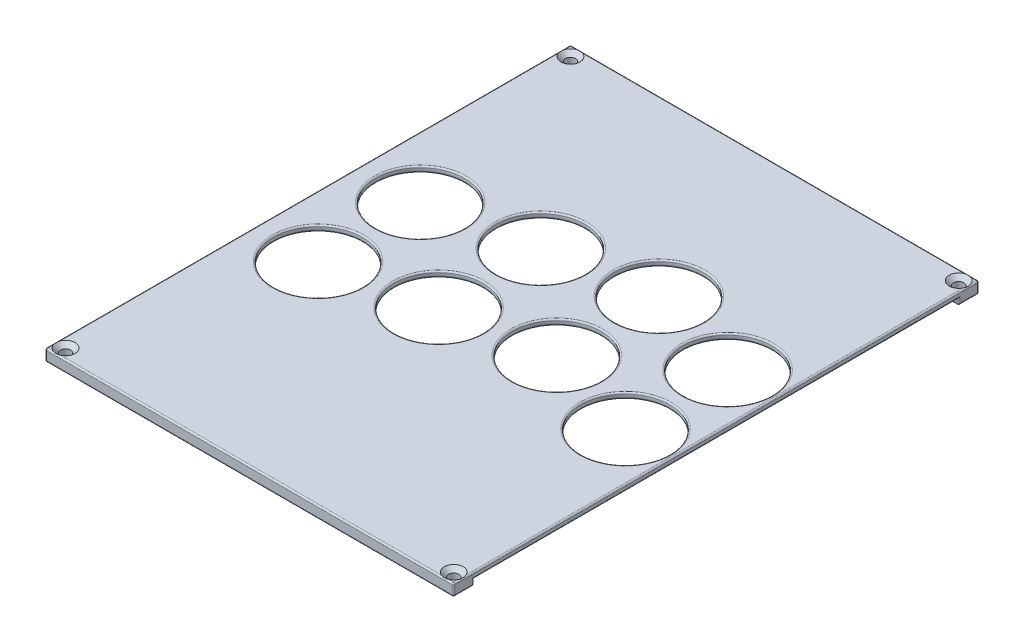
SolidWorks part; units mm, degrees
ref_plane "Front Plane" through (0, 0, 0) normal (0, 0, 1) x (1, 0, 0)
ref_plane "Top Plane" through (0, 0, 0) normal (0, 1, 0) x (1, 0, 0)
ref_plane "Right Plane" through (0, 0, 0) normal (1, 0, 0) x (0, 0, -1)
sketch "Sketch1" plane through (0, 0, 0) normal (0, 1, 0) x (1, 0, 0)
  line L0 (-119, -72.5) -> (-84.7071, -65.5) construction
  line L1 (0, 0) -> (-140, 0)
  line L2 (0, 0) -> (0, -180)
  line L3 (0, -180) -> (-140, -180)
  line L4 (-140, 0) -> (-140, -180)
  line L5 (-84.7071, -65.5) -> (-50.2253, -59.5) construction
  line L6 (-50.2253, -59.5) -> (-16.6842, -69.5) construction
  line L7 (-16.6842, -69.5) -> (-16.6842, -104.5) construction
  line L8 (-16.6842, -104.5) -> (-50.2253, -94.5) construction
  line L9 (-50.2253, -94.5) -> (-84.7071, -100.5) construction
  line L10 (-84.7071, -100.5) -> (-119, -107.5) construction
  line L11 (-119, -107.5) -> (-119, -72.5) construction
  line L12 (-84.7071, -100.5) -> (-84.7071, -65.5) construction
  line L13 (-50.2253, -94.5) -> (-50.2253, -59.5) construction
  line L14 (-16.6842, -69.5) -> (-16.6842, -59.5) construction
  line L15 (-16.6842, -59.5) -> (-50.2253, -59.5) construction
  line L16 (-50.2253, -59.5) -> (-84.7071, -59.5) construction
  line L17 (-84.7071, -65.5) -> (-84.7071, -59.5) construction
  line L18 (-84.7071, -65.5) -> (-119, -65.5) construction
  line L19 (-119, -65.5) -> (-119, -72.5) construction
  line L20 (-119, -72.5) -> (-140, -72.5) construction
  line L21 (-119, -72.5) -> (-119, 0) construction
  line L22 (-16.6842, -69.5) -> (0, -69.5) construction
  line L23 (-70, -145) -> (-140, -145) construction
  line L24 (-140, -173) -> (-133, -173) construction
  line L25 (-133, -173) -> (-133, -180) construction
  line L26 (-7, -180) -> (-7, -173) construction
  line L27 (-7, -173) -> (0, -173) construction
  line L28 (0, -7) -> (-7, -7) construction
  line L29 (-7, -7) -> (-7, 0) construction
  line L30 (-133, 0) -> (-133, -7) construction
  line L31 (-133, -7) -> (-140, -7) construction
  line L32 (-133, -7) -> (-140, 0) construction
  line L33 (-7, -7) -> (0, 0) construction
  line L34 (-7, -173) -> (0, -180) construction
  line L35 (-140, -180) -> (-133, -173) construction
  line L36 (-119, -107.5) -> (-119, -180) construction
  line L37 (-42.5, -162) -> (-97.5, -162) construction
  line L38 (-42.5, -162) -> (-42.5, -128) construction
  line L39 (-42.5, -128) -> (-97.5, -128) construction
  line L40 (-97.5, -162) -> (-97.5, -128) construction
  line L41 (-42.5, -162) -> (-97.5, -128) construction
  line L42 (-42.5, -128) -> (-97.5, -162) construction
  line L43 (-70, -145) -> (0, -145) construction
  line L44 (-70, -145) -> (-70, -180) construction
  line L45 (-133, -2) -> (-7, -2)
  line L46 (-95.1329, -128) -> (-96.3164, -125.95)
  line L47 (-96.3164, -125.95) -> (-98.6836, -125.95)
  line L48 (-98.6836, -125.95) -> (-99.8671, -128)
  line L49 (-99.8671, -128) -> (-98.6836, -130.05)
  line L50 (-98.6836, -130.05) -> (-96.3164, -130.05)
  line L51 (-96.3164, -130.05) -> (-95.1329, -128)
  line L52 (-40.1329, -128) -> (-41.3164, -125.95)
  line L53 (-41.3164, -125.95) -> (-43.6836, -125.95)
  line L54 (-43.6836, -125.95) -> (-44.8671, -128)
  line L55 (-44.8671, -128) -> (-43.6836, -130.05)
  line L56 (-43.6836, -130.05) -> (-41.3164, -130.05)
  line L57 (-41.3164, -130.05) -> (-40.1329, -128)
  line L58 (-41.3164, -164.05) -> (-40.1329, -162)
  line L59 (-40.1329, -162) -> (-41.3164, -159.95)
  line L60 (-41.3164, -159.95) -> (-43.6836, -159.95)
  line L61 (-43.6836, -159.95) -> (-44.8671, -162)
  line L62 (-44.8671, -162) -> (-43.6836, -164.05)
  line L63 (-43.6836, -164.05) -> (-41.3164, -164.05)
  line L64 (-95.1329, -162) -> (-96.3164, -159.95)
  line L65 (-96.3164, -159.95) -> (-98.6836, -159.95)
  line L66 (-98.6836, -159.95) -> (-99.8671, -162)
  line L67 (-99.8671, -162) -> (-98.6836, -164.05)
  line L68 (-98.6836, -164.05) -> (-96.3164, -164.05)
  line L69 (-96.3164, -164.05) -> (-95.1329, -162)
  line L70 (-101, -166) -> (-39, -166)
  line L71 (-101, -166) -> (-101, -124)
  line L72 (-101, -124) -> (-39, -124)
  line L73 (-39, -166) -> (-39, -124)
  line L74 (-101, -166) -> (-39, -124) construction
  line L75 (-101, -124) -> (-39, -166) construction
  line L76 (-138, -7) -> (-138, -173)
  line L77 (-133, -178) -> (-7, -178)
  line L78 (-133, -2) -> (-133, -7)
  line L79 (-133, -7) -> (-138, -7)
  line L80 (-7, -2) -> (-7, -7)
  line L81 (-7, -7) -> (0, -7)
  line L82 (0, -173) -> (-7, -173)
  line L83 (-7, -173) -> (-7, -178)
  line L84 (-133, -178) -> (-133, -173)
  line L85 (-133, -173) -> (-138, -173)
  circle A16 centre (-119, -72.5) radius 15 construction
  circle A17 centre (-84.7071, -65.5) radius 15 construction
  circle A18 centre (-50.2253, -59.5) radius 15 construction
  circle A19 centre (-16.6842, -69.5) radius 15 construction
  circle A20 centre (-119, -107.5) radius 15 construction
  circle A21 centre (-84.7071, -100.5) radius 15 construction
  circle A22 centre (-50.2253, -94.5) radius 15 construction
  circle A23 centre (-16.6842, -104.5) radius 15 construction
  circle A24 centre (-119, -72.5) radius 15.2
  circle A25 centre (-84.7071, -65.5) radius 15.2
  circle A26 centre (-50.2253, -59.5) radius 15.2
  circle A27 centre (-16.6842, -69.5) radius 15.2
  circle A28 centre (-16.6842, -104.5) radius 15.2
  circle A29 centre (-50.2253, -94.5) radius 15.2
  circle A30 centre (-84.7071, -100.5) radius 15.2
  circle A31 centre (-119, -107.5) radius 15.2
  circle A32 centre (-136.5, -3.5) radius 1.75
  circle A33 centre (-3.5, -3.5) radius 1.75
  circle A34 centre (-3.5, -176.5) radius 1.75
  circle A35 centre (-136.5, -176.5) radius 1.75
  circle A36 centre (-97.5, -128) radius 2.05 construction
  circle A37 centre (-42.5, -128) radius 2.05 construction
  circle A38 centre (-42.5, -162) radius 2.05 construction
  circle A39 centre (-97.5, -162) radius 2.05 construction
  point P23 (-70, -145)
  dimension "D1" = 30
  dimension "D7" = 3.5
  dimension "D14" = 4.1
  dimension "D3" = 10
  dimension "D4" = 6
  dimension "D5" = 7
  dimension "D6" = 7
  dimension "D8" = 0.2
  dimension "D2" = 35
  dimension "D9" = 180
  dimension "D10" = 140
  dimension "D11" = 55
  dimension "D12" = 34
  dimension "D13" = 35
  dimension "D15" = 42
  dimension "D16" = 62
  dimension "D17" = 2
  dimension "D18" = 2
  dimension "D19" = 2
  dimension "D20" = 21
extrude "Boss-Extrude1" add sketch "Sketch1" along normal blind 2 contours L1 L4 L3 L2 A35 A34 A33 A32 A31 A30 A29 A28 A27 A26 A25 A24 L73 L70 L71 L72 | L70 L73 L72 L71 L51 L50 L49 L48 L47 L46 L57 L56 L55 L54 L53 L52 L63 L62 L61 L60 L59 L58 L69 L68 L67 L66 L65 L64 | L68 L69 L64 L65 L66 L67 | L84 L85 L76 L79 L78 L45 L80 L81 L2 L1 L4 L3 L82 L83 L77 A35 A34 A33 A32 | L48 L49 L50 L51 L46 L47 | L52 L53 L54 L55 L56 L57 | L58 L59 L60 L61 L62 L63 region at (-0.228, 0, 3.5) region at (-69.4107, 0, 83.0298) region at (-97.5, 0, 162) region at (-70, 0, 145)
extrude "Boss-Extrude2" add sketch "Sketch1<4>" against normal blind 2 contours L84 L85 L76 L79 L78 L45 L80 L81 L2 L1 L4 L3 L82 L83 L77 A35 A34 A33 A32 | L70 L73 L72 L71 L51 L50 L49 L48 L47 L46 L57 L56 L55 L54 L53 L52 L63 L62 L61 L60 L59 L58 L69 L68 L67 L66 L65 L64 region at (-0.228, 0, 3.5) region at (-70, 0, 145)
sketch "Sketch1<4>" plane through (0, 0, 0) normal (0, 1, 0) x (1, 0, 0) same geometry as "Sketch1"
sketch "Sketch2" plane through (0, 0, 0) normal (1, 0, 0) x (0, 0, -1)
  line L9 (-180, 2) -> (0, 2)
  line L13 (0, 2) -> (0, -2)
  line L14 (0, -2) -> (-7, -2) construction
  line L15 (0, -2) -> (-7, -2)
  line L16 (-7, -2) -> (-7, 0)
  line L17 (-7, 0) -> (-173, 0)
  line L18 (-173, 0) -> (-173, -2)
  line L19 (-173, -2) -> (-180, -2)
  line L22 (-180, -2) -> (-180, 2)
  line M2 (0, -2) -> (0, 2)
  line M4 (-180, 2) -> (-180, -2)
  line M9 (-173, 0) -> (-7, 0)
  line M10 (0, 2) -> (-180, 2)
  line M24 (-7, 0) -> (-7, -2)
  line M25 (-7, -2) -> (0, -2)
  line M26 (-180, -2) -> (-173, -2)
  line M27 (-173, -2) -> (-173, 0)
extrude "Cut-Extrude1" cut sketch "Sketch2" against normal blind 0.1 contours M27 M9 M24 M25 M2 M10 M4 M26 region at (0, 0.8557, 90)
fillet "Fillet1" radius 0.5 83 edges at (-140, 0, 0) (-140, 0, 180) (-70.05, 2, 0) (-0.1, 0, 0) (-140, 2, 90) (-70.05, 2, 180) (-0.1, 0, 180) (-16.6842, 0, 119.7) (-16.6842, 2, 119.7) (-16.6842, 0, 84.7) (-16.6842, 2, 84.7) (-50.2253, 0, 74.7) (-50.2253, 2, 74.7) (-50.2253, 0, 109.7) (-50.2253, 2, 109.7) (-84.7071, 0, 115.7) (-84.7071, 2, 115.7) (-84.7071, 0, 80.7) (-84.7071, 2, 80.7) (-119, 0, 87.7) (-119, 2, 87.7) (-119, 0, 122.7) (-119, 2, 122.7) (-39, -2, 145) (-70, -2, 124) (-101, -2, 145) (-70, -2, 166) (-97.5, -2, 164.05) (-99.2754, -2, 163.025) (-99.2754, -2, 160.975) (-97.5, -2, 159.95) (-95.7246, -2, 160.975) (-95.7246, -2, 163.025) (-44.2754, -2, 163.025) (-44.2754, -2, 160.975) (-42.5, -2, 159.95) (-40.7246, -2, 160.975) (-40.7246, -2, 163.025) (-42.5, -2, 164.05) (-42.5, -2, 130.05) (-44.2754, -2, 129.025) (-44.2754, -2, 126.975) (-42.5, -2, 125.95) (-40.7246, -2, 126.975) (-40.7246, -2, 129.025) (-97.5, -2, 130.05) (-99.2754, -2, 129.025) (-99.2754, -2, 126.975) (-97.5, -2, 125.95) (-95.7246, -2, 126.975) (-95.7246, -2, 129.025) (-0.1, 2, 90) (-0.1, 0, 90) (-101, -1, 124) (-101, -1, 166) (-39, -1, 124) (-39, -1, 166) (-70.05, -2, 0) (-140, -2, 90) (-70.05, -2, 180) (-0.1, -2, 176.5) (-0.1, -2, 3.5) (-0.1, -1, 7) (-0.1, -1, 173) (-7, -1, 7) (-3.55, -2, 173) (-7, -2, 175.5) (-70, -2, 178) (-133, -2, 175.5) (-135.5, -2, 173) (-138, -2, 90) (-135.5, -2, 7) (-133, -2, 4.5) (-70, -2, 2) (-7, -2, 4.5) (-3.55, -2, 7) (-136.5, -2, 5.25) (-3.5, -2, 5.25) (-3.5, -2, 178.25) (-136.5, -2, 178.25) (-133, -1, 7) (-133, -1, 173) (-7, -1, 173)
chamfer "Chamfer1" distance 1.5 angle 45 4 edges at (-136.5, 2, 178.25) (-3.5, 2, 178.25) (-3.5, 2, 5.25) (-136.5, 2, 5.25)
